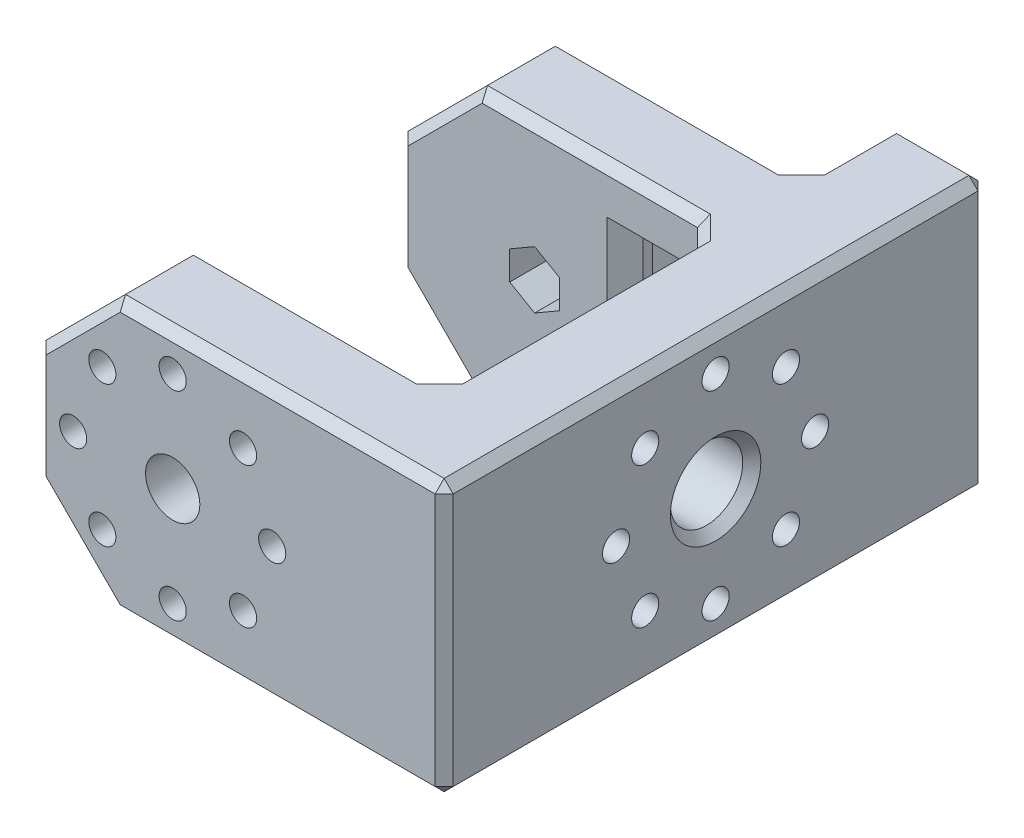
SolidWorks part; units mm, degrees
ref_plane "Alzado" through (0, 0, 0) normal (0, 0, 1) x (1, 0, 0)
ref_plane "Planta" through (0, 0, 0) normal (0, 1, 0) x (1, 0, 0)
ref_plane "Vista lateral" through (0, 0, 0) normal (1, 0, 0) x (0, 0, -1)
sketch "Croquis1" plane through (0, 0, 0) normal (0, 0, 1) x (1, 0, 0)
  line L0 (6.2132, 15) -> (30, 15)
  line L1 (15, -6.2132) -> (15, 6.2132) construction
  line L2 (15, 6.2132) -> (6.2132, 15) construction
  line L3 (6.2132, 15) -> (-6.2132, 15)
  line L4 (-6.2132, 15) -> (-15, 6.2132)
  line L5 (-15, 6.2132) -> (-15, -6.2132)
  line L6 (-15, -6.2132) -> (-6.2132, -15)
  line L7 (-6.2132, -15) -> (6.2132, -15)
  line L8 (6.2132, -15) -> (15, -6.2132) construction
  line L9 (30, 15) -> (30, -15)
  line L10 (30, -15) -> (6.2132, -15)
  circle A0 centre (0, 0) radius 15 construction
  dimension "D1" = 30
  dimension "D2" = 15
extrude "Saliente-Extruir1" add sketch "Croquis1" along normal blind 60
sketch "Croquis2" plane through (0, 15, 0) normal (0, 1, 0) x (1, 0, 0)
  line L0 (-15, -60) -> (-15, 0) construction
  line L1 (-15, -50.5) -> (20, -50.5)
  line L2 (-15, -50.5) -> (-15, -20)
  line L3 (-15, -20) -> (20, -20)
  line L4 (20, -50.5) -> (20, -20)
  line L5 (30, 0) -> (-6.2132, 0) construction
  line L6 (-15, -10.5) -> (20, -10.5)
  line L7 (-15, -10.5) -> (-15, 0)
  line L8 (-15, 0) -> (20, 0)
  line L9 (20, -10.5) -> (20, 0)
  line L10 (30, -60) -> (-6.2132, -60) construction
  line L11 (30, -60) -> (30, 0) construction
  dimension "D1" = 9.5
  dimension "D2" = 30.5
  dimension "D3" = 9.5
  dimension "D4" = 10
extrude "Cortar-Extruir1" cut sketch "Croquis2" against normal through all
sketch "Croquis3" plane through (0, 0, 60) normal (0, 0, 1) x (1, 0, 0)
  circle A0 centre (0, 0) radius 3
  dimension "D1" = 6
extrude "Cortar-Extruir2" cut sketch "Croquis3" against normal up to next
sketch "Croquis12" plane through (0, 0, 10.5) normal (0, 0, -1) x (-1, 0, 0)
  circle A0 centre (0, 0) radius 6
  dimension "D1" = 12
extrude "Saliente-Extruir2" add sketch "Croquis12" along normal blind 1
sketch "Croquis4" plane through (0, 0, 9.5) normal (0, 0, -1) x (-1, 0, 0)
  circle A0 centre (0, 0) radius 1.5
  dimension "D1" = 3
extrude "Cortar-Extruir3" cut sketch "Croquis4" against normal up to next
sketch "Croquis5" plane through (0, 0, 20) normal (0, 0, 1) x (1, 0, 0)
  line L1 (0, 3.1754) -> (-2.75, 1.5877)
  line L2 (-2.75, 1.5877) -> (-2.75, -1.5877)
  line L3 (-2.75, -1.5877) -> (0, -3.1754)
  line L4 (0, -3.1754) -> (2.75, -1.5877)
  line L5 (2.75, -1.5877) -> (2.75, 1.5877)
  line L6 (2.75, 1.5877) -> (0, 3.1754)
  circle A0 centre (0, 0) radius 2.75 construction
  dimension "D1" = 5.5
extrude "Cortar-Extruir4" cut sketch "Croquis5" against normal blind 5
sketch "Croquis9" plane through (0, 0, 20) normal (0, 0, 1) x (1, 0, 0)
  line L0 (20, -15) -> (20, 15) construction
  line L1 (20, -10) -> (10, -10)
  line L2 (20, -10) -> (20, 10)
  line L3 (20, 10) -> (10, 10)
  line L4 (10, -10) -> (10, 10)
  line L5 (-6.2132, -15) -> (30, -15) construction
  line L6 (30, 15) -> (-6.2132, 15) construction
  dimension "D1" = 5
  dimension "D2" = 5
  dimension "D3" = 10
extrude "Cortar-Extruir7" cut sketch "Croquis9" against normal blind 5
sketch "Croquis7" plane through (30, 0, 0) normal (1, 0, 0) x (0, 0, -1)
  line L0 (-60, 0) -> (0, 0) construction
  line L1 (-60, -15) -> (-60, 15) construction
  line L2 (-30, 15) -> (-30, -15) construction
  line L3 (-60, 15) -> (0, 15) construction
  line L4 (-60, -15) -> (0, -15) construction
  circle A0 centre (-30, 0) radius 4
  circle A1 centre (-30, 11) radius 1.5
  circle A2 centre (-22.2218, 7.7782) radius 1.5
  circle A3 centre (-19, 0) radius 1.5
  circle A4 centre (-22.2218, -7.7782) radius 1.5
  circle A5 centre (-30, -11) radius 1.5
  circle A6 centre (-37.7782, -7.7782) radius 1.5
  circle A7 centre (-41, 0) radius 1.5
  circle A8 centre (-37.7782, 7.7782) radius 1.5
  point P31 (-30, 0)
  dimension "D1" = 3
  dimension "D2" = 8
  dimension "D4" = 11
  dimension "D3" = 8
extrude "Cortar-Extruir5" cut sketch "Croquis7" against normal up to next
sketch "Croquis8" plane through (30, 0, 0) normal (1, 0, 0) x (0, 0, -1)
  line L0 (-19.9765, 5.5328) -> (-19.1546, 8.6)
  line L1 (-26.8246, 11) -> (-28.4123, 13.75)
  line L2 (-28.4123, 13.75) -> (-31.5877, 13.75)
  line L3 (-31.5877, 13.75) -> (-33.1754, 11)
  line L4 (-33.1754, 11) -> (-31.5877, 8.25)
  line L5 (-31.5877, 8.25) -> (-28.4123, 8.25)
  line L6 (-28.4123, 8.25) -> (-26.8246, 11)
  line L7 (-19.1546, 8.6) -> (-21.4, 10.8454)
  line L8 (-21.4, 10.8454) -> (-24.4672, 10.0235)
  line L9 (-24.4672, 10.0235) -> (-25.2891, 6.9563)
  line L10 (-25.2891, 6.9563) -> (-23.0437, 4.7109)
  line L11 (-23.0437, 4.7109) -> (-19.9765, 5.5328)
  line L12 (-19, -3.1754) -> (-16.25, -1.5877)
  line L13 (-16.25, -1.5877) -> (-16.25, 1.5877)
  line L14 (-16.25, 1.5877) -> (-19, 3.1754)
  line L15 (-19, 3.1754) -> (-21.75, 1.5877)
  line L16 (-21.75, 1.5877) -> (-21.75, -1.5877)
  line L17 (-21.75, -1.5877) -> (-19, -3.1754)
  line L18 (-24.4672, -10.0235) -> (-21.4, -10.8454)
  line L19 (-21.4, -10.8454) -> (-19.1546, -8.6)
  line L20 (-19.1546, -8.6) -> (-19.9765, -5.5328)
  line L21 (-19.9765, -5.5328) -> (-23.0437, -4.7109)
  line L22 (-23.0437, -4.7109) -> (-25.2891, -6.9563)
  line L23 (-25.2891, -6.9563) -> (-24.4672, -10.0235)
  line L24 (-33.1754, -11) -> (-31.5877, -13.75)
  line L25 (-31.5877, -13.75) -> (-28.4123, -13.75)
  line L26 (-28.4123, -13.75) -> (-26.8246, -11)
  line L27 (-26.8246, -11) -> (-28.4123, -8.25)
  line L28 (-28.4123, -8.25) -> (-31.5877, -8.25)
  line L29 (-31.5877, -8.25) -> (-33.1754, -11)
  line L30 (-40.0235, -5.5328) -> (-40.8454, -8.6)
  line L31 (-40.8454, -8.6) -> (-38.6, -10.8454)
  line L32 (-38.6, -10.8454) -> (-35.5328, -10.0235)
  line L33 (-35.5328, -10.0235) -> (-34.7109, -6.9563)
  line L34 (-34.7109, -6.9563) -> (-36.9563, -4.7109)
  line L35 (-36.9563, -4.7109) -> (-40.0235, -5.5328)
  line L36 (-41, 3.1754) -> (-43.75, 1.5877)
  line L37 (-43.75, 1.5877) -> (-43.75, -1.5877)
  line L38 (-43.75, -1.5877) -> (-41, -3.1754)
  line L39 (-41, -3.1754) -> (-38.25, -1.5877)
  line L40 (-38.25, -1.5877) -> (-38.25, 1.5877)
  line L41 (-38.25, 1.5877) -> (-41, 3.1754)
  line L42 (-35.5328, 10.0235) -> (-38.6, 10.8454)
  line L43 (-38.6, 10.8454) -> (-40.8454, 8.6)
  line L44 (-40.8454, 8.6) -> (-40.0235, 5.5328)
  line L45 (-40.0235, 5.5328) -> (-36.9563, 4.7109)
  line L46 (-36.9563, 4.7109) -> (-34.7109, 6.9563)
  line L47 (-34.7109, 6.9563) -> (-35.5328, 10.0235)
  circle A0 centre (-30, 11) radius 2.75 construction
  point P54 (-30, 0)
  dimension "D1" = 5.5
  dimension "D2" = 8
extrude "Cortar-Extruir6" cut sketch "Croquis8" against normal up to next from offset 5 offset against normal yes
sketch "Croquis10" plane through (0, 0, 60) normal (0, 0, 1) x (1, 0, 0)
  circle A0 centre (0, 11) radius 1.5
  circle A1 centre (0, 0) radius 3 construction
  circle A2 centre (7.7782, 7.7782) radius 1.5
  circle A3 centre (11, 0) radius 1.5
  circle A4 centre (7.7782, -7.7782) radius 1.5
  circle A5 centre (0, -11) radius 1.5
  circle A6 centre (-7.7782, -7.7782) radius 1.5
  circle A7 centre (-11, 0) radius 1.5
  circle A8 centre (-7.7782, 7.7782) radius 1.5
  point P21 (0, 0)
  dimension "D1" = 3
  dimension "D2" = 11
  dimension "D3" = 8
extrude "Cortar-Extruir8" cut sketch "Croquis10" against normal up to next
sketch "Croquis11" plane through (0, 0, 60) normal (0, 0, 1) x (1, 0, 0)
  line L0 (10.0235, 5.5328) -> (10.8454, 8.6)
  line L1 (3.1754, 11) -> (1.5877, 13.75)
  line L2 (1.5877, 13.75) -> (-1.5877, 13.75)
  line L3 (-1.5877, 13.75) -> (-3.1754, 11)
  line L4 (-3.1754, 11) -> (-1.5877, 8.25)
  line L5 (-1.5877, 8.25) -> (1.5877, 8.25)
  line L6 (1.5877, 8.25) -> (3.1754, 11)
  line L7 (10.8454, 8.6) -> (8.6, 10.8454)
  line L8 (8.6, 10.8454) -> (5.5328, 10.0235)
  line L9 (5.5328, 10.0235) -> (4.7109, 6.9563)
  line L10 (4.7109, 6.9563) -> (6.9563, 4.7109)
  line L11 (6.9563, 4.7109) -> (10.0235, 5.5328)
  line L12 (11, -3.1754) -> (13.75, -1.5877)
  line L13 (13.75, -1.5877) -> (13.75, 1.5877)
  line L14 (13.75, 1.5877) -> (11, 3.1754)
  line L15 (11, 3.1754) -> (8.25, 1.5877)
  line L16 (8.25, 1.5877) -> (8.25, -1.5877)
  line L17 (8.25, -1.5877) -> (11, -3.1754)
  line L18 (5.5328, -10.0235) -> (8.6, -10.8454)
  line L19 (8.6, -10.8454) -> (10.8454, -8.6)
  line L20 (10.8454, -8.6) -> (10.0235, -5.5328)
  line L21 (10.0235, -5.5328) -> (6.9563, -4.7109)
  line L22 (6.9563, -4.7109) -> (4.7109, -6.9563)
  line L23 (4.7109, -6.9563) -> (5.5328, -10.0235)
  line L24 (-3.1754, -11) -> (-1.5877, -13.75)
  line L25 (-1.5877, -13.75) -> (1.5877, -13.75)
  line L26 (1.5877, -13.75) -> (3.1754, -11)
  line L27 (3.1754, -11) -> (1.5877, -8.25)
  line L28 (1.5877, -8.25) -> (-1.5877, -8.25)
  line L29 (-1.5877, -8.25) -> (-3.1754, -11)
  line L30 (-10.0235, -5.5328) -> (-10.8454, -8.6)
  line L31 (-10.8454, -8.6) -> (-8.6, -10.8454)
  line L32 (-8.6, -10.8454) -> (-5.5328, -10.0235)
  line L33 (-5.5328, -10.0235) -> (-4.7109, -6.9563)
  line L34 (-4.7109, -6.9563) -> (-6.9563, -4.7109)
  line L35 (-6.9563, -4.7109) -> (-10.0235, -5.5328)
  line L36 (-11, 3.1754) -> (-13.75, 1.5877)
  line L37 (-13.75, 1.5877) -> (-13.75, -1.5877)
  line L38 (-13.75, -1.5877) -> (-11, -3.1754)
  line L39 (-11, -3.1754) -> (-8.25, -1.5877)
  line L40 (-8.25, -1.5877) -> (-8.25, 1.5877)
  line L41 (-8.25, 1.5877) -> (-11, 3.1754)
  line L42 (-5.5328, 10.0235) -> (-8.6, 10.8454)
  line L43 (-8.6, 10.8454) -> (-10.8454, 8.6)
  line L44 (-10.8454, 8.6) -> (-10.0235, 5.5328)
  line L45 (-10.0235, 5.5328) -> (-6.9563, 4.7109)
  line L46 (-6.9563, 4.7109) -> (-4.7109, 6.9563)
  line L47 (-4.7109, 6.9563) -> (-5.5328, 10.0235)
  circle A0 centre (0, 11) radius 2.75 construction
  circle A1 centre (7.7782, 7.7782) radius 2.75 construction
  circle A2 centre (11, 0) radius 2.75 construction
  circle A3 centre (7.7782, -7.7782) radius 2.75 construction
  circle A4 centre (0, -11) radius 2.75 construction
  circle A5 centre (-7.7782, -7.7782) radius 2.75 construction
  circle A6 centre (-11, 0) radius 2.75 construction
  circle A7 centre (-7.7782, 7.7782) radius 2.75 construction
  point P67 (0, 0)
  dimension "D1" = 5.5
  dimension "D2" = 8
extrude "Cortar-Extruir9" cut sketch "Croquis11" against normal up to next from offset 5 offset against normal yes
chamfer "Chaflán5" distance 0.5 angle 45 1 edges at (-1.5, 0, 9.5)
chamfer "Chaflán6" distance 1 angle 45 1 edges at (6, 0, 10.5)
chamfer "Chaflán4" distance 1 angle 45 2 edges at (30, 4, 30) (20, 4, 30)
chamfer "Chaflán3" distance 1 angle 45 1 edges at (3, 0, 50.5)
chamfer "Chaflán1" distance 2 angle 45 7 edges at (20, 0, 50.5) (20, -12.5, 20) (20, 12.5, 20) (20, 0, 10.5) (20, 0, 15) (10, 0, 20) (10, 0, 15)
chamfer "Chaflán2" distance 1 angle 45 37 edges at (19, -15, 21) (20, -15, 35.25) (19, -15, 49.5) (5.8934, -15, 50.5) (-10.6066, -10.6066, 50.5) (5.8934, -15, 20) (-10.6066, -10.6066, 20) (-15, 0, 20) (-10.6066, 10.6066, 20) (5.8934, 15, 20) (-15, 0, 50.5) (-10.6066, 10.6066, 50.5) (20, 15, 35.25) (5.8934, 15, 50.5) (19, 15, 49.5) (-10.6066, 10.6066, 60) (-15, 0, 60) (-10.6066, -10.6066, 60) (11.8934, -15, 60) (30, -15, 30) (30, 0, 0) (25, -15, 0) (-15, 0, 10.5) (-10.6066, -10.6066, 10.5) (5.8934, -15, 10.5) (19, -15, 9.5) (20, -15, 4.25) (20, 0, 0) (-10.6066, 10.6066, 10.5) (5.8934, 15, 10.5) (19, 15, 9.5) (20, 15, 4.25) (25, 15, 0) (11.8934, 15, 60) (30, 0, 60) (30, 15, 30) (19, 15, 21)
